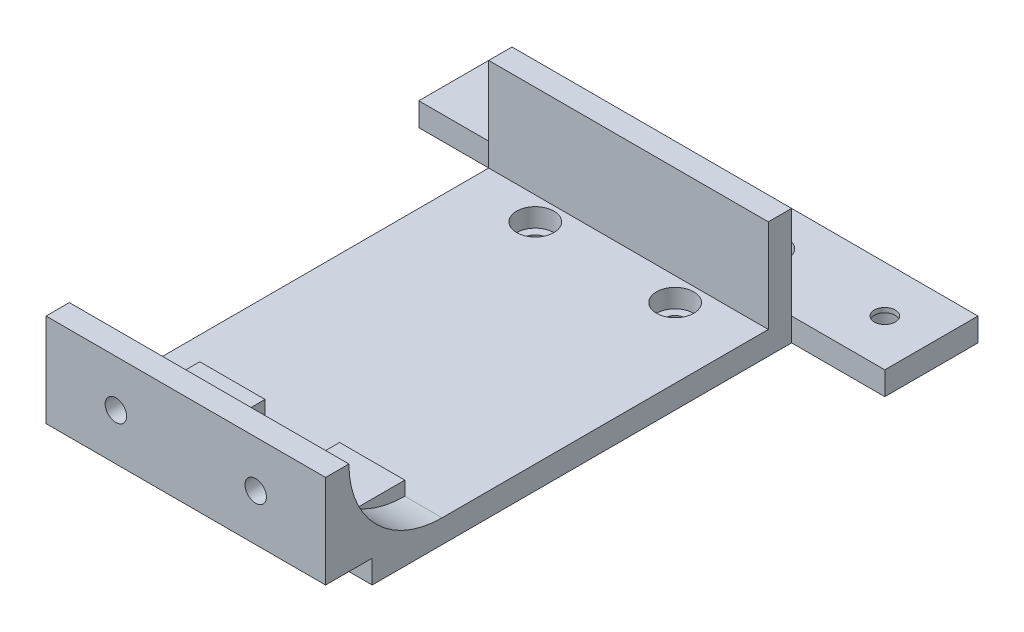
SolidWorks part; units mm, degrees
material "사용자정의 플라스틱"
ref_plane "정면" through (0, 0, 0) normal (0, 0, 1) x (1, 0, 0)
ref_plane "윗면" through (0, 0, 0) normal (0, 1, 0) x (1, 0, 0)
ref_plane "우측면" through (0, 0, 0) normal (1, 0, 0) x (0, 0, -1)
sketch "스케치1" plane through (0, 0, 0) normal (0, 0, 1) x (1, 0, 0)
  line L1 (-30, 10) -> (30, 10)
  line L2 (-30, 10) -> (-30, -10)
  line L3 (-30, -10) -> (30, -10)
  line L4 (30, 10) -> (30, -10)
  line L5 (-30, 10) -> (30, -10) construction
  line L6 (-30, -10) -> (30, 10) construction
  point P0 (0, 0)
  dimension "D1" = 20
  dimension "D2" = 60
extrude "보스-돌출1" add sketch "스케치1" along normal blind 20
sketch "스케치2" plane through (0, -10, 0) normal (0, -1, 0) x (1, 0, 0)
  line L0 (30, 20) -> (30, 0) construction
  line L1 (-30, 20) -> (30, 20)
  line L2 (-30, 20) -> (-30, -20)
  line L3 (-30, -20) -> (30, -20)
  line L4 (30, 20) -> (30, -20)
  dimension "D1" = 0
  dimension "D2" = 40
extrude "보스-돌출2" add sketch "스케치2" along normal blind 5
ref_plane "평면1" through (0, 0, 0) normal (-1, 0, 0) x (0, 0, 1)
sketch "스케치3" plane through (30, 0, 0) normal (1, 0, 0) x (0, 0, -1)
  line L1 (20, -15) -> (0, -15)
  line L2 (20, -15) -> (20, -10)
  line L3 (20, -10) -> (0, -10)
  line L4 (0, -15) -> (0, -10)
extrude "보스-돌출3" add sketch "스케치3" along normal blind 20
mirror "대칭 복사1" about plane through (0, 0, 0) normal (-1, 0, 0) of "보스-돌출3"
hole_wizard "M4 소켓 머리 캡 나사용 카운터보어2" positions "스케치6" profile "스케치7" counterbore size "M4" standard "KS" end condition through all
sketch "스케치6" plane through (0, -15, 0) normal (0, -1, 0) x (-1, 0, 0)
  line L0 (-50, 0) -> (-30, 0) construction
  line L1 (50, 0) -> (30, 0) construction
  line L2 (50, 0) -> (50, 20) construction
  line L3 (-50, 0) -> (-50, 20) construction
  point P0 (40, 10)
  point P2 (-40, 10)
  dimension "D1" = 10
  dimension "D2" = 10
  dimension "D3" = 10
  dimension "D4" = 10
sketch "스케치7" plane through (-40, -15, -10) normal (1, 0, 0) x (0, 0, -1)
  line L0 (0, 0) -> (0, 25)
  line L1 (0, 25) -> (2.25, 25)
  line L3 (2.25, 25) -> (2.25, 4)
  line L4 (2.25, 4) -> (4, 4)
  line L5 (4, 4) -> (4, 0)
  line L7 (4, 0) -> (0, 0)
  line L11 (0, -6.35) -> (0, 107.95) construction
  dimension "관통 구멍 지름" = 4.5
  dimension "관통 구멍 깊이" = 25
  dimension "카운터보어 지름" = 8
  dimension "카운터보어 깊이" = 4
sketch "스케치8" plane through (30, 0, 0) normal (1, 0, 0) x (0, 0, -1)
  line L0 (0, -10) -> (0, 10) construction
  line L1 (-20, 10) -> (-5, 10)
  line L2 (-20, 10) -> (-20, -10)
  line L3 (-20, -10) -> (-5, -10)
  line L4 (-5, 10) -> (-5, -10)
  dimension "D1" = 0
  dimension "D2" = 5
extrude "컷-돌출1" cut sketch "스케치8" against normal through all
hole_wizard "M4 소켓 머리 캡 나사용 카운터보어1" positions "스케치4" profile "스케치5" counterbore size "M4" standard "KS" end condition through all
sketch "스케치4" plane through (0, -10, 0) normal (0, 1, 0) x (1, 0, 0)
  line L0 (-50, 20) -> (50, 20) construction
  line L1 (0, 13.75) -> (0, -13.75) construction
  line L2 (-30, -20) -> (30, -20) construction
  line L3 (30, -20) -> (30, -5) construction
  line L4 (-30, -20) -> (-30, -5) construction
  point P0 (-15, 10)
  point P2 (15, 10)
  point P11 (-15, -10)
  point P13 (15, -10)
  dimension "D1" = 10
  dimension "D2" = 10
  dimension "D3" = 15
  dimension "D4" = 15
  dimension "D5" = 10
  dimension "D6" = 10
  dimension "D7" = 15
  dimension "D8" = 15
sketch "스케치5" plane through (-15, -10, -10) normal (1, 0, 0) x (0, 0, 1)
  line L0 (0, 0) -> (0, 5)
  line L1 (0, 5) -> (2.25, 5)
  line L3 (2.25, 5) -> (2.25, 4)
  line L4 (2.25, 4) -> (4, 4)
  line L5 (4, 4) -> (4, 0)
  line L7 (4, 0) -> (0, 0)
  line L11 (0, -6.35) -> (0, 107.95) construction
  dimension "관통 구멍 지름" = 4.5
  dimension "관통 구멍 깊이" = 5
  dimension "카운터보어 지름" = 8
  dimension "카운터보어 깊이" = 4
sketch "스케치10" plane through (0, 0, 20) normal (0, 0, 1) x (1, 0, 0)
  line L1 (-30, -15) -> (30, -15)
  line L2 (-30, -15) -> (-30, -10)
  line L3 (-30, -10) -> (30, -10)
  line L4 (30, -15) -> (30, -10)
extrude "보스-돌출4" add sketch "스케치10" along normal blind 80
sketch "스케치11" plane through (0, -10, 0) normal (0, 1, 0) x (1, 0, 0)
  line L0 (30, -100) -> (30, -5) construction
  line L1 (-30, -100) -> (30, -100)
  line L2 (-30, -100) -> (-30, -95)
  line L3 (-30, -95) -> (30, -95)
  line L4 (30, -100) -> (30, -95)
  dimension "D1" = 5
extrude "보스-돌출5" add sketch "스케치11" along normal blind 20
fillet "필렛1" radius 20 1 edges at (0, -10, 95)
sketch "스케치12" plane through (-30, 0, 0) normal (-1, 0, 0) x (0, 0, 1)
  line L1 (100, -15) -> (90, -15)
  line L2 (100, -15) -> (100, -10)
  line L3 (100, -10) -> (90, -10)
  line L4 (90, -15) -> (90, -10)
  dimension "D1" = 10
  dimension "D2" = 5
extrude "컷-돌출2" cut sketch "스케치12" against normal through all
ref_plane "평면2" through (0, 0, 60) normal (0, 0, 1) x (1, 0, 0)
sketch "스케치13" plane through (0, 0, 60) normal (0, 0, 1) x (1, 0, 0)
  line L0 (30, -10) -> (-30, -10) construction
  line L1 (-22, -10) -> (-8, -10)
  line L2 (-22, -10) -> (-22, 10)
  line L3 (-22, 10) -> (-8, 10)
  line L4 (-8, -10) -> (-8, 10)
  line L5 (-30, 10) -> (-30, -10) construction
  line L6 (8, -10) -> (22, -10)
  line L7 (8, -10) -> (8, 10)
  line L8 (8, 10) -> (22, 10)
  line L9 (22, -10) -> (22, 10)
  line L10 (0, 13.75) -> (0, -13.75) construction
  line L11 (-30, 10) -> (30, 10) construction
  line L12 (-30, 10) -> (30, 10) construction
  line L13 (30, -10) -> (30, 10) construction
  dimension "D1" = 8
  dimension "D2" = 8
  dimension "D3" = 0
  dimension "D4" = 0
  dimension "D5" = 8
  dimension "D6" = 8
extrude "컷-돌출3" cut sketch "스케치13" along normal blind 35
sketch "스케치14" plane through (0, 0, 95) normal (0, 0, -1) x (-1, 0, 0)
  line L0 (-8, -10) -> (-22, -10) construction
  line L1 (-8, -10) -> (-22, -10)
  line L2 (-8, -10) -> (-8, -7)
  line L3 (-8, -7) -> (-22, -7)
  line L4 (-22, -10) -> (-22, -7)
  line L5 (-22, -10) -> (-22, 10) construction
  line L6 (-8, 10) -> (-8, -10) construction
  line L7 (22, 10) -> (22, -10) construction
  line L8 (8, -10) -> (22, -10)
  line L9 (8, -10) -> (8, -7)
  line L10 (8, -7) -> (22, -7)
  line L11 (22, -10) -> (22, -7)
  dimension "D1" = 0
  dimension "D2" = 0
  dimension "D3" = 3
  dimension "D4" = 3
extrude "보스-돌출6" add sketch "스케치14" along normal blind 20
hole_wizard "M4 여유 구멍1" positions "스케치15" profile "스케치16" hole size "M4" standard "KS" end condition through all
sketch "스케치15" plane through (0, 0, 95) normal (0, 0, -1) x (-1, 0, 0)
  line L0 (-22, 10) -> (-8, 10) construction
  line L1 (8, 10) -> (22, 10) construction
  line L2 (8, -7) -> (8, 10) construction
  line L3 (-8, 10) -> (-8, -7) construction
  point P0 (-15, 0)
  point P2 (15, 0)
  point P13 (17.739, 0.312)
  dimension "D1" = 10
  dimension "D2" = 10
  dimension "D3" = 7
  dimension "D4" = 7
sketch "스케치16" plane through (15, 0, 95) normal (1, 0, 0) x (0, 1, 0)
  line L0 (0, 0) -> (0, 5)
  line L1 (0, 5) -> (2.3, 5)
  line L2 (2.3, 5) -> (2.3, 0)
  line L5 (2.3, 0) -> (0, 0)
  line L11 (0, -6.35) -> (0, 107.95) construction
  dimension "관통 구멍 지름" = 4.6
  dimension "관통 구멍 깊이" = 5
